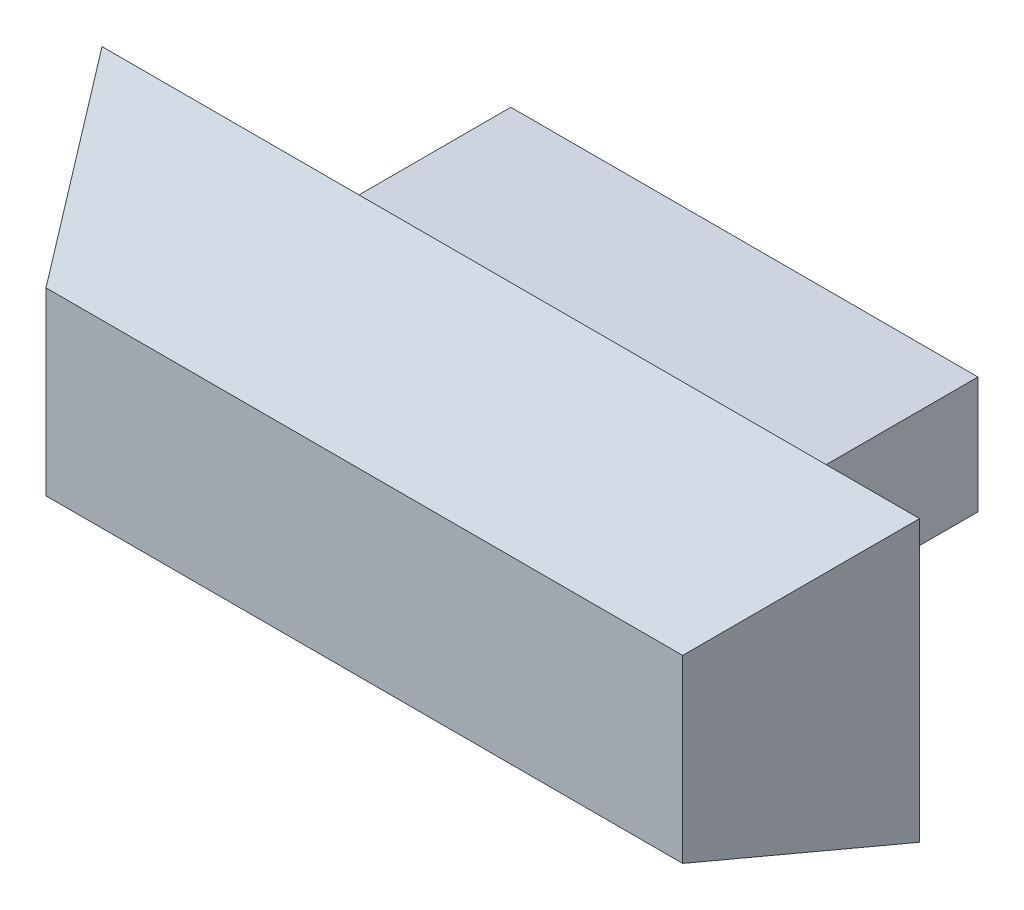
SolidWorks part; units mm, degrees
material "PET"
ref_plane "Front Plane" through (0, 0, 0) normal (0, 0, 1) x (1, 0, 0)
ref_plane "Top Plane" through (0, 0, 0) normal (0, 1, 0) x (1, 0, 0)
ref_plane "Right Plane" through (0, 0, 0) normal (1, 0, 0) x (0, 0, -1)
sketch "Sketch1" plane through (0, 0, 0) normal (0, 0, 1) x (1, 0, 0)
  line L1 (83.5025, 67.437) -> (72.39, 67.437)
  line L2 (83.5025, 67.437) -> (83.5025, 63.627)
  line L3 (83.5025, 63.627) -> (72.39, 63.627)
  line L4 (72.39, 67.437) -> (72.39, 63.627)
  dimension "D1" = 3.81
  dimension "D2" = 11.1125
extrude "Boss-Extrude1" add sketch "Sketch1" along normal blind 2.54
chamfer "Chamfer1" distance 2.54 angle 35 1 edges at (72.39, 65.532, 2.54) first distance on face at (72.39, 65.532, 1.27)
chamfer "Chamfer2" distance 2.54 angle 15 3 edges at (78.8355, 63.627, 2.54) (83.5025, 65.532, 2.54) (78.8355, 67.437, 2.54) first distance on face at (78.3909, 63.627, 1.27) first distance on face at (83.5025, 65.532, 1.27) first distance on face at (78.3909, 67.437, 1.27)
sketch "Sketch2" plane through (0, 0, 0) normal (0, 0, -1) x (-1, 0, 0)
  line L0 (-83.5025, 65.532) -> (-72.39, 65.532) construction
  line L1 (-83.5025, 63.627) -> (-83.5025, 67.437) construction
  line L2 (-72.39, 67.437) -> (-72.39, 63.627) construction
  line L4 (-74.7712, 64.7383) -> (-81.1212, 64.7383)
  line L5 (-74.7712, 64.7383) -> (-74.7712, 66.3258)
  line L6 (-74.7712, 66.3258) -> (-81.1212, 66.3258)
  line L7 (-81.1212, 64.7383) -> (-81.1212, 66.3258)
  line L8 (-74.7712, 64.7383) -> (-81.1212, 66.3258) construction
  line L9 (-74.7712, 66.3258) -> (-81.1212, 64.7383) construction
  point P6 (-77.9462, 65.532)
  dimension "D1" = 1.5875
  dimension "D2" = 6.35
extrude "Boss-Extrude2" add sketch "Sketch2" along normal blind 3.175
